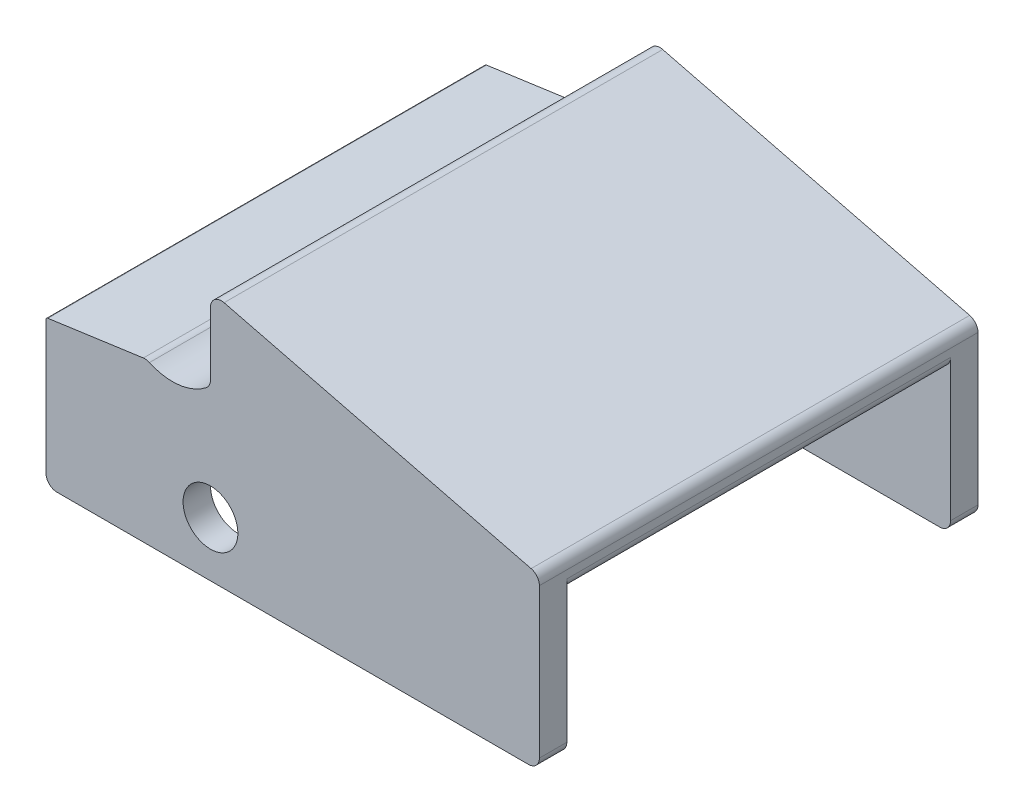
SolidWorks part; units mm, degrees
ref_plane "Front Plane" through (0, 0, 0) normal (0, 0, 1) x (1, 0, 0)
ref_plane "Top Plane" through (0, 0, 0) normal (0, 1, 0) x (1, 0, 0)
ref_plane "Right Plane" through (0, 0, 0) normal (1, 0, 0) x (0, 0, -1)
sketch "Sketch1" plane through (0, 0, 0) normal (0, 0, 1) x (1, 0, 0)
  line L0 (28.575, 11.3665) -> (-9.525, 20.8915)
  line L1 (-28.575, -8.1915) -> (28.575, -8.1915)
  line L2 (-28.575, -8.1915) -> (-28.575, 8.1915)
  line L3 (-28.575, 8.1915) -> (28.575, 8.1915)
  line L4 (28.575, -8.1915) -> (28.575, 8.1915)
  line L5 (-28.575, -8.1915) -> (28.575, 8.1915) construction
  line L6 (-28.575, 8.1915) -> (28.575, -8.1915) construction
  line L7 (-28.575, 8.1915) -> (28.575, 8.1915)
  line L9 (-9.525, 11.3665) -> (28.575, 11.3665)
  line L10 (28.575, 8.1915) -> (28.575, 11.3665)
  line L11 (-9.525, 20.8915) -> (-9.525, 11.3665)
  line L12 (-28.575, 8.1915) -> (-28.575, 8.6995)
  line L13 (-28.575, 8.6995) -> (-9.525, 11.3665)
  circle A0 centre (-9.525, -1.8415) radius 3.175
  arc A1 (-9.525, 11.3665) -> (-16.9108, 10.3325) centre (-13.9305, 15.9396) cw
  point P0 (0, 0)
  dimension "D3" = 6.35
  dimension "D9" = 6.35
  dimension "D1" = 38.1
  dimension "D2" = 19.05
  dimension "D4" = 10.033
  dimension "D5" = 6.35
  dimension "D6" = 3.175
  dimension "D7" = 12.7
  dimension "D8" = 0.508
extrude "Boss-Extrude1" add sketch "Sketch1" along normal mid plane 50.8 contours L1 L4 L3 L2 A0 | L9 L3 L10 | L0 L11 L9 region at (3.175, 14.5415, 0) region at (4.3051, 9.6366, 0) region at (0.3335, 0.0645, 0)
extrude "Cut-Extrude1" cut sketch "Sketch1<4>" against normal mid plane 44.45 contours L1 L4 L3 L2 A0 region at (0.3335, 0.0645, 0)
sketch "Sketch1<4>" plane through (0, 0, 0) normal (0, 0, 1) x (1, 0, 0) same geometry as "Sketch1"
fillet "Fillet2" radius 1.27 9 edges at (28.575, 8.1915, 0) (28.575, 11.3665, 0) (-9.525, 20.8915, 0) (-28.575, -8.1915, 23.8125) (-28.575, -8.1915, -23.8125) (28.575, -8.1915, -23.8125) (28.575, -8.1915, 23.8125) (-16.9108, 10.3325, 0) (-9.525, 11.3665, 0)
fillet "Fillet3" radius 0.254 2 edges at (-28.575, 8.1915, 0) (-28.575, 8.6995, 0)
